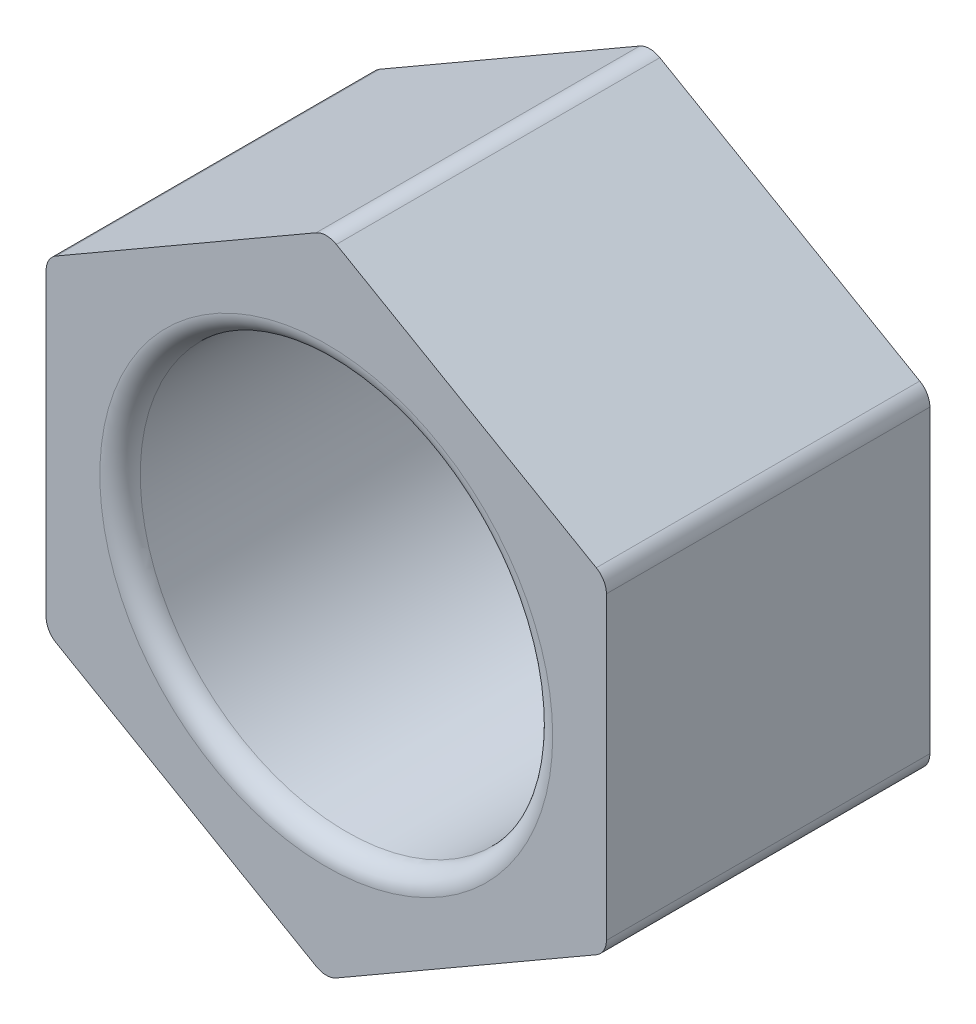
SolidWorks part; units mm, degrees
ref_plane "Front Plane" through (0, 0, 0) normal (0, 0, 1) x (1, 0, 0)
ref_plane "Top Plane" through (0, 0, 0) normal (0, 1, 0) x (1, 0, 0)
ref_plane "Right Plane" through (0, 0, 0) normal (1, 0, 0) x (0, 0, -1)
sketch "Sketch1" plane through (0, 0, 0) normal (0, 0, 1) x (1, 0, 0)
  line L1 (0, 4) -> (-3.4641, 2)
  line L2 (-3.4641, 2) -> (-3.4641, -2)
  line L3 (-3.4641, -2) -> (0, -4)
  line L4 (0, -4) -> (3.4641, -2)
  line L5 (3.4641, -2) -> (3.4641, 2)
  line L6 (3.4641, 2) -> (0, 4)
  circle A0 centre (0, 0) radius 3.4641 construction
  dimension "D1" = 8
extrude "Boss-Extrude1" add sketch "Sketch1" along normal blind 4
sketch "Sketch2" plane through (0, 0, 4) normal (0, 0, 1) x (1, 0, 0)
  circle A0 centre (0, 0) radius 2.55
  dimension "D1" = 5.1
extrude "Cut-Extrude1" cut sketch "Sketch2" against normal through all
fillet "Fillet1" radius 0.25 8 edges at (2.55, 0, 4) (2.55, 0, 0) (-3.4641, 2, 2) (-3.4641, -2, 2) (0, -4, 2) (3.4641, -2, 2) (3.4641, 2, 2) (0, 4, 2)
